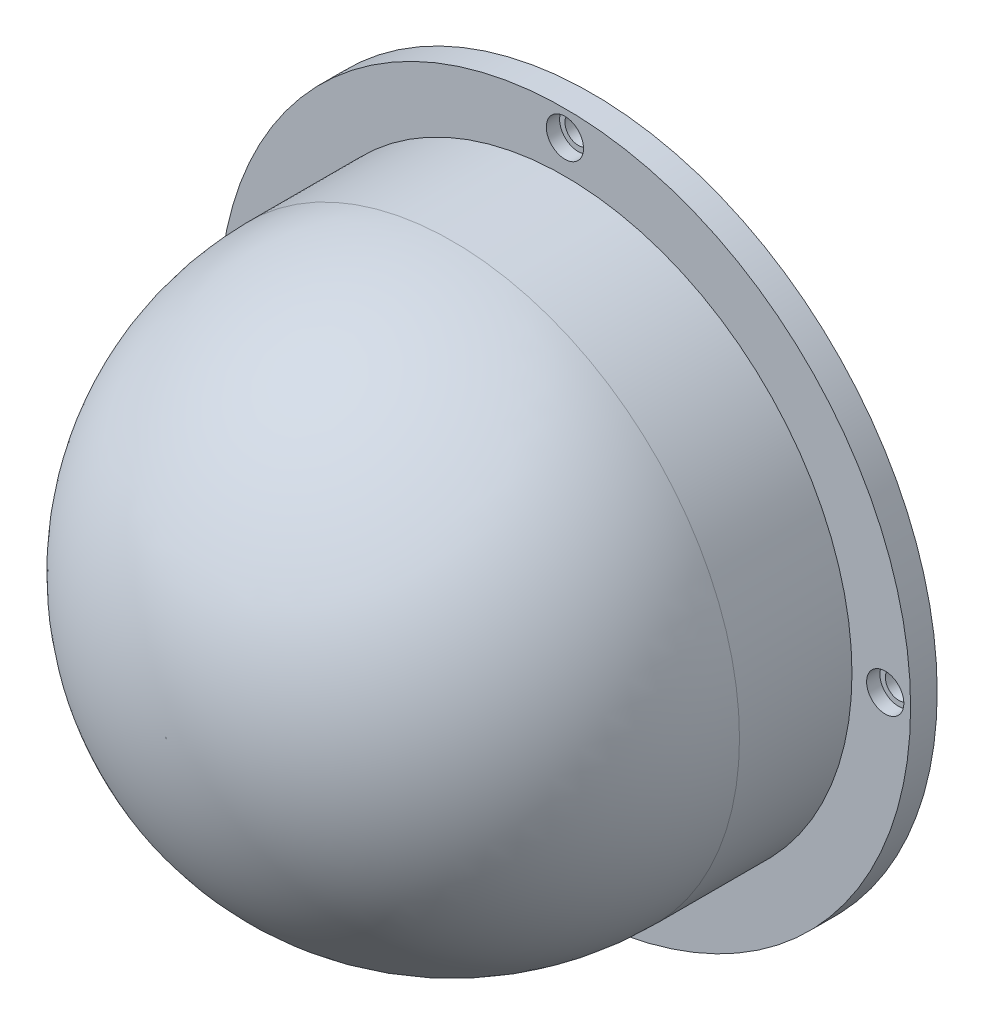
SolidWorks part; units mm, degrees
ref_plane "Front Plane" through (0, 0, 0) normal (1, 0, 0) x (0, 1, 0)
ref_plane "Top Plane" through (0, 0, 0) normal (0, 0, 1) x (0, 1, 0)
ref_plane "Right Plane" through (0, 0, 0) normal (0, 1, 0) x (-1, 0, 0)
sketch "Sketch2" plane through (0, 0, 0) normal (0, 0, 1) x (0, 1, 0)
  circle A0 centre (0, 0) radius 65
  dimension "D1" = 130
extrude "Boss-Extrude1" add sketch "Sketch2" along normal blind 5
sketch "Sketch3" plane through (0, 0, 5) normal (0, 0, 1) x (1, 0, 0)
  circle A0 centre (0, 0) radius 53.975
  dimension "D1" = 107.95
extrude "Boss-Extrude2" add sketch "Sketch3" along normal blind 75
fillet "Fillet7" radius 53.848 1 edges at (53.975, 0, 80)
shell "Shell1" thickness 5 removed face at (65, 0, 0)
sketch "Sketch7" plane through (0, 0, 5) normal (0, 0, 1) x (1, 0, 0)
  circle A0 centre (0, 60.2478) radius 2.5
  dimension "D1" = 5
extrude "Cut-Extrude2" cut sketch "Sketch7" against normal blind 5
sketch "Sketch8" plane through (0, 0, 5) normal (0, 0, 1) x (1, 0, 0)
  circle A0 centre (0, 60.2236) radius 3.5
  dimension "D1" = 7
extrude "Cut-Extrude3" cut sketch "Sketch8" against normal blind 2.5
pattern_circular "CirPattern1" count 4 over 360 about axis through (0, 0, 5) along (0, 0, -1) of "Cut-Extrude3", "Cut-Extrude2" reverse direction yes
